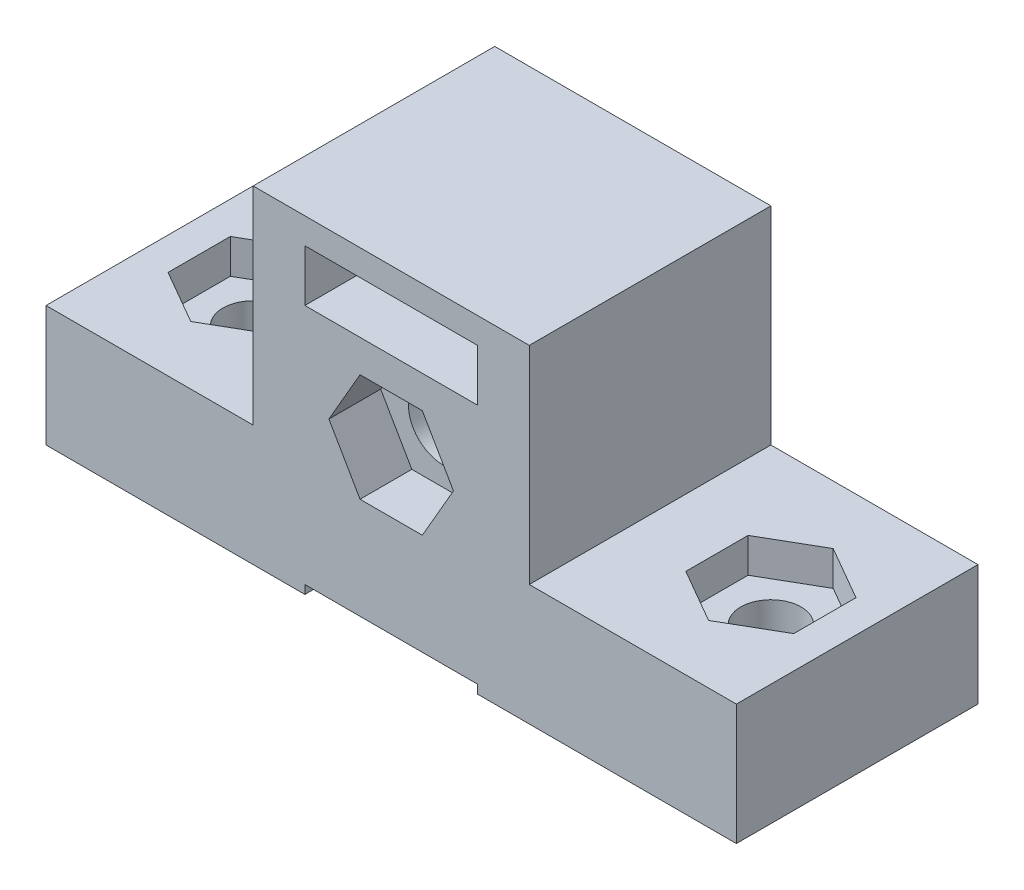
SolidWorks part; units mm, degrees
ref_plane "Front Plane" through (0, 0, 0) normal (0, 0, 1) x (1, 0, 0)
ref_plane "Top Plane" through (0, 0, 0) normal (0, 1, 0) x (1, 0, 0)
ref_plane "Right Plane" through (0, 0, 0) normal (1, 0, 0) x (0, 0, -1)
sketch "Sketch1" plane through (0, 0, 0) normal (0, 1, 0) x (1, 0, 0)
  line L1 (-20, 7) -> (20, 7)
  line L2 (-20, 7) -> (-20, -7)
  line L3 (-20, -7) -> (20, -7)
  line L4 (20, 7) -> (20, -7)
  line L5 (-20, 7) -> (20, -7) construction
  line L6 (-20, -7) -> (20, 7) construction
  point P0 (0, 0)
  dimension "D1" = 40
  dimension "D2" = 14
extrude "Boss-Extrude1" add sketch "Sketch1" along normal blind 19
sketch "Sketch2" plane through (0, 0, 7) normal (0, 0, 1) x (1, 0, 0)
  line L0 (0, 19) -> (0, 0) construction
  line L1 (-20, 19) -> (20, 19) construction
  line L3 (-5, 14.5) -> (5, 14.5)
  line L4 (-5, 14.5) -> (-5, 17.5)
  line L5 (-5, 17.5) -> (5, 17.5)
  line L6 (5, 14.5) -> (5, 17.5)
  line L7 (-5, 14.5) -> (5, 17.5) construction
  line L8 (-5, 17.5) -> (5, 14.5) construction
  line L9 (-5, -0.5) -> (5, -0.5)
  line L10 (-5, -0.5) -> (-5, 0.5)
  line L11 (-5, 0.5) -> (5, 0.5)
  line L12 (5, -0.5) -> (5, 0.5)
  line L13 (-5, -0.5) -> (5, 0.5) construction
  line L14 (-5, 0.5) -> (5, -0.5) construction
  point P5 (0, 16)
  dimension "D1" = 10
  dimension "D2" = 3
  dimension "D3" = 16
  dimension "D4" = 10
  dimension "D5" = 1
extrude "Cut-Extrude1" cut sketch "Sketch2" against normal blind 30
sketch "Sketch3" plane through (0, 0, 7) normal (0, 0, 1) x (1, 0, 0)
  line L0 (0, 19) -> (0, 0) construction
  line L1 (-20, 19) -> (20, 19) construction
  circle A0 centre (0, 9.5) radius 2
  dimension "D1" = 4
extrude "Cut-Extrude2" cut sketch "Sketch3" against normal through all
sketch "Sketch4" plane through (0, 19, 0) normal (0, 1, 0) x (1, 0, 0)
  line L0 (-20, 0) -> (20, 0) construction
  line L1 (-20, 7) -> (-20, -7) construction
  line L2 (20, -7) -> (20, 7) construction
  line L3 (0, 7) -> (0, -7) construction
  line L4 (20, 7) -> (-20, 7) construction
  line L5 (-20, -7) -> (20, -7) construction
  circle A0 centre (-15, 0) radius 1.75
  circle A1 centre (15, 0) radius 1.75
  dimension "D1" = 3.5
  dimension "D2" = 15
extrude "Cut-Extrude3" cut sketch "Sketch4" against normal through all
sketch "Sketch8" plane through (0, 0, 0) normal (0, -1, 0) x (-1, 0, 0)
  line L0 (-5, 7) -> (-5, -7) construction
  line L1 (5, -7) -> (-5, -7)
  line L2 (5, -7) -> (5, -6)
  line L3 (5, -6) -> (-5, -6)
  line L4 (-5, -7) -> (-5, -6)
  dimension "D1" = 1
extrude "Boss-Extrude2" [suppressed] add sketch "Sketch8" against normal up to next
sketch "Sketch9" plane through (0, 19, 0) normal (0, 1, 0) x (1, 0, 0)
  line L0 (0, 7) -> (0, -7) construction
  line L1 (-15, 3.6084) -> (-18.125, 1.8042)
  line L2 (-18.125, 1.8042) -> (-18.125, -1.8042)
  line L3 (-18.125, -1.8042) -> (-15, -3.6084)
  line L4 (-15, -3.6084) -> (-11.875, -1.8042)
  line L5 (-11.875, -1.8042) -> (-11.875, 1.8042)
  line L6 (-11.875, 1.8042) -> (-15, 3.6084)
  line L7 (20, 7) -> (-20, 7) construction
  line L8 (-20, -7) -> (20, -7) construction
  line L9 (11.875, 1.8042) -> (15, 3.6084)
  line L10 (11.875, -1.8042) -> (11.875, 1.8042)
  line L11 (15, -3.6084) -> (11.875, -1.8042)
  line L12 (18.125, -1.8042) -> (15, -3.6084)
  line L13 (18.125, 1.8042) -> (18.125, -1.8042)
  line L14 (15, 3.6084) -> (18.125, 1.8042)
  circle A0 centre (-15, 0) radius 3.125 construction
  circle A1 centre (15, 0) radius 3.125 construction
  dimension "D1" = 6.25
extrude "Cut-Extrude4" cut sketch "Sketch9" against normal offset from surface (14 mm away) 5 up to face at (15, 0, -1.75)
sketch "Sketch10" plane through (0, 0, 7) normal (0, 0, 1) x (1, 0, 0)
  line L1 (1.8042, 12.625) -> (-1.8042, 12.625)
  line L2 (-1.8042, 12.625) -> (-3.6084, 9.5)
  line L3 (-3.6084, 9.5) -> (-1.8042, 6.375)
  line L4 (-1.8042, 6.375) -> (1.8042, 6.375)
  line L5 (1.8042, 6.375) -> (3.6084, 9.5)
  line L6 (3.6084, 9.5) -> (1.8042, 12.625)
  circle A0 centre (0, 9.5) radius 3.125 construction
  dimension "D1" = 6.25
extrude "Cut-Extrude5" cut sketch "Sketch10" against normal blind 3
sketch "Sketch11" plane through (0, 0, 7) normal (0, 0, 1) x (1, 0, 0)
  line L0 (0, 19) -> (0, 0) construction
  line L1 (-20, 19) -> (-8, 19)
  line L2 (-20, 19) -> (-20, 7)
  line L3 (-20, 7) -> (-8, 7)
  line L4 (-8, 19) -> (-8, 7)
  line L5 (-20, 19) -> (20, 19) construction
  line L6 (-20, 0) -> (-5, 0) construction
  line L7 (8, 19) -> (8, 7)
  line L8 (20, 7) -> (8, 7)
  line L9 (20, 19) -> (20, 7)
  line L10 (20, 19) -> (8, 19)
  dimension "D1" = 8
  dimension "D2" = 7
extrude "Cut-Extrude6" cut sketch "Sketch11" against normal through all
equation "\"X-ROD-SPACING\"=45"
equation "\"Y-ROD-SPACING\"=75"
equation "\"Z-ROD-SPACING\"=17.5"
equation "\"Y-BED-OFFSET\"=2"
equation "\"Y-BED-ROD-INSET\"=3.5"
equation "\"Y-BED-SCREW-SPACING\"=209"
equation "\"Y-BED-SCREW-CUTOUT-SLOT-HEIGHT\"=2.5"
equation "\"T-SLOT-NUT-FILLET-RADIUS\"=0.5"
equation "\"T-SLOT-SCREW-SHAFT-RADIUS\"=1.55"
equation "\"T-SLOT-SCREW-SHAFT-CUTOUT-LENGTH\"=11"
equation "\"T-SLOT-NUT-DEPTH\"=3.5"
equation "\"T-SLOT-NUT-WIDTH\"=2.85"
equation "\"T-SLOT-NUT-END-DISTANCE\"=8"
equation "\"ACRYLIC-THICKNESS\"=10"
equation "\"ACRYLIC-THICKNESS2\"=4.5"
equation "\"ACRYLIC-TAB-CUTOUT-SIZE\"=\"ACRYLIC-THICKNESS\"+\"ACRYLIC-TAB-TOLERANCE\"*2"
equation "\"ACRYLIC-TAB-TOLERANCE\"=-.05"
equation "\"ACRYLIC-TAB-WIDTH\"=\"ACRYLIC-THICKNESS\""
equation "\"ACRYLIC-M3-HOLE\"=2.9"
equation "\"SMOOTHROD-CAP-SCREW-DISTANCE\"=20"
equation "\"FRAME-WIDTH-INNER\"=370"
equation "\"NEMA17-HOLE-SPACING\"=31"
equation "\"NEMA17-CENTRAL-CUTOUT\"=22.5"
equation "\"Z-BRACKET-REACH\"=57"
equation "\"Z-ROD-INSET\"=13.5"
equation "\"TOP-BRACKET-SPACING\"=40"
equation "\"SMOOTHROD-X-LENGTH\"=350"
equation "\"SMOOTHROD-Y-LENGTH\"=350"
equation "\"SMOOTHROD-Z-LENGTH\"=350"
equation "\"SMOOTHROD-TIGHTENING-HEADROOM\"=.25"
equation "\"LEADSCREW-Z-LENGTH\"=300"
equation "\"SCREW-LENGTH-FRAME\"=\"ACRYLIC-THICKNESS\" + 10"
equation "\"SCREW-LENGTH-MOTOR\"=\"ACRYLIC-THICKNESS\" + 5"
equation "\"SCREW-LENGTH-EXTRUDER\"=28"
equation "\"SCREW-HEAD-RADIUS\"=6"
equation "\"PRINTED-M3-HOLE\"=3.5"
equation "\"PRINTED-X-SMOOTHROD-DIAMETER\"=8.8"
equation "\"PRINTED-X-SMOOTHROD-CUTOUT\"=10"
equation "\"PRINTED-X-BASE-HEIGHT\"=10"
equation "\"PRINTED-LM8UU-CUTOUT-SIZE\"=15.5"
equation "\"PRINTED-LM8UU-CUTOUT-LENGTH\"=24.5"
equation "\"PRINTED-X-IDLER-HEIGHT\"=16"
equation "\"PSU-MOUNTING-WIDTH\"=95"
equation "\"PSU-MOUNTING-HEIGHT\"=177"
equation "\"Y-BELT-TO-ROD-DISTANCE\"=20"
equation "\"SPOOL-HOLDER-ROD-SPACING\"=150"
equation "\"ACRYLIC-X-CARRIAGE-WIDTH\"=55"
equation "\"ACRYLIC-X-CARRIAGE-HEIGHT\"=75"
equation "\"ACRYLIC-X-CARRIAGE-LM8UU-CUTOUT-WIDTH\"=24.25"
equation "\"ACRYLIC-X-CARRIAGE-LM8UU-CUTOUT-HEIGHT\"=11.0"
equation "\"ACRYLIC-X-CARRIAGE-SCREW-SPACING-X\"=15"
equation "\"ACRYLIC-X-CARRIAGE-SCREW-SPACING-Y\"=33"
equation "\"ACRYLIC-X-CARRIAGE-CENTER-TAB-SPACING\"=14"
equation "\"ACRYLIC-X-CARRIAGE-EXTRUDER-OFFSET\"=26"
equation "\"ACRYLIC-X-CARRIAGE-EXTRUDER-ANGLE\"=90"
equation "\"ACRYLIC-X-CARRIAGE-EXTRUDER-SHELF-DEPTH\"=\"ACRYLIC-X-CARRIAGE-EXTRUDER-OFFSET\" + 28"
equation "\"ACRYLIC-X-CARRIAGE-EXTRUDER-BRACE-SPACING\"=23"
equation "\"ACRYLIC-X-CARRIAGE-EXTRUDER-BRACE-TAB-OFFSET\"=20"
equation "\"ACRYLIC-X-CARRIAGE-EXTRUDER-BRACE-HEIGHT\"=35"
equation "\"ACRYLIC-X-CARRIAGE-EXTRUDER-BRACE-SCREW-SPACING\"=22"
equation "\"ACRYLIC-X-CARRIAGE-DUAL-WIDTH-MULTIPLIER\"=1.65"
equation "\"ACRYLIC-X-CARRIAGE-DUAL-HOTEND-SPACING\"=42"
equation "\"ACRYLIC-X-CARRIAGE-DUAL-WIDTH\"=75"
equation "\"ACRYLIC-X-CARRIAGE-DUAL-HOTEND-SEPARATION\"=36"
equation "\"ACRYLIC-X-CARRIAGE-DUAL-MOUNT-PLATE-DEPTH\"=75"
equation "\"ACRYLIC-X-CARRIAGE-DUAL-MOUNT-BRACE-WIDTH\"=33"
equation "\"ACRYLIC-X-CARRIAGE-DUAL-MOUNT-SCREW-WIDTH\"=40"
equation "\"BLOWER-FAN-WIDTH\"=15"
equation "\"PRINTED-M3-NUT-AF\"=6.25"
equation "\"D1@Sketch9\"=\"PRINTED-M3-NUT-AF\""
equation "\"D1@Sketch10\"=\"PRINTED-M3-NUT-AF\""
equation "\"D1@Sketch4\"=\"PRINTED-M3-HOLE\""
